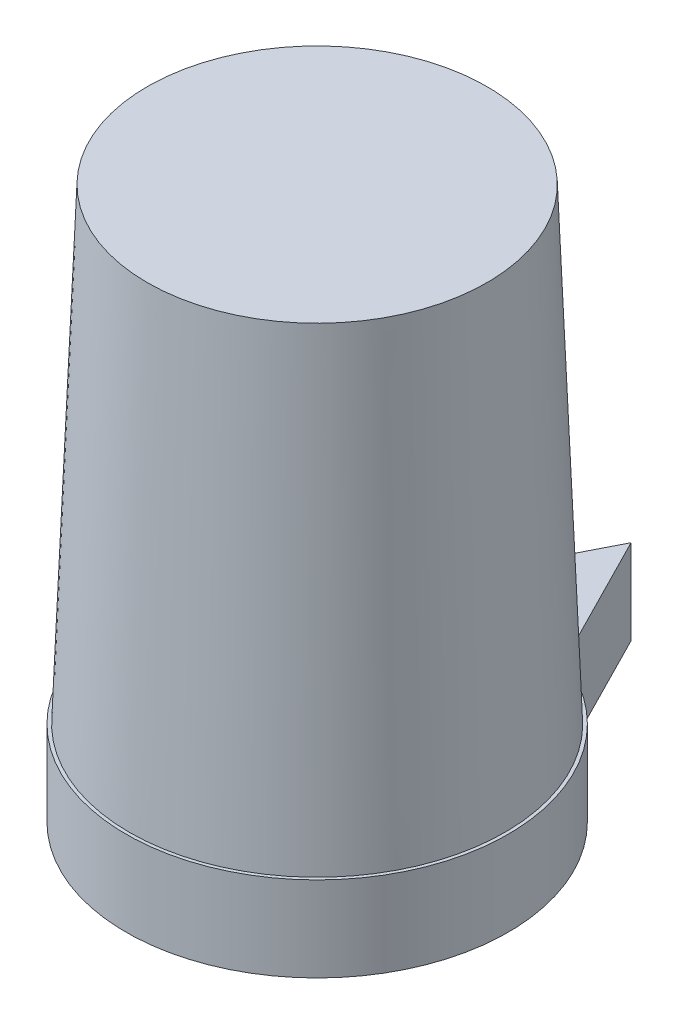
SolidWorks part; units mm, degrees
note: The reader was unsure of these and kept them because the rebuilt part matched: shared geometry of "Sketch1<35>", "Sketch1<36>".
ref_plane "Plan de face" through (0, 0, 0) normal (0, 0, 1) x (1, 0, 0)
ref_plane "Plan de dessus" through (0, 0, 0) normal (0, 1, 0) x (1, 0, 0)
ref_plane "Plan de droite" through (0, 0, 0) normal (1, 0, 0) x (0, 0, -1)
sketch "Sketch1" plane through (0, 0, 0) normal (0, 1, 0) x (1, 0, 0)
  line L0 (-3.4771, 0.4) -> (3.4771, 0.4)
  line L1 (-4.95, 0) -> (4.95, 0) construction
  line L2 (-3.4771, -0.4) -> (3.4771, -0.4)
  line L3 (-1.6263, 4.1959) -> (0, 7.3927)
  line L4 (0, -4.95) -> (0, 4.95) construction
  line L5 (1.6263, 4.1959) -> (0, 7.3927)
  circle A0 centre (0, 0) radius 3.5
  circle A1 centre (0, 0) radius 4.5
  point P12 (0, 0)
  point P16 (0, 7.945)
  point P17 (-1.6263, 4.1959)
  point P18 (0, 7.3927)
  dimension "D1" = 7
  dimension "D2" = 9
  dimension "D3" = 0.4
ref_plane "Plane1" through (0, 13, 0) normal (0, 1, 0) x (1, 0, 0)
sketch "Sketch2" plane through (0, 13, 0) normal (0, 1, 0) x (1, 0, 0)
  circle A0 centre (0, 0) radius 4
  dimension "D1" = 8
loft "Loft1" add profiles "Sketch2" section "Sketch2" section "Sketch1" connector at (-2.8461, 13, 2.8107) connector at (-3.4528, 0, 2.8858)
extrude "Boss-Extrude1" add sketch "Sketch1<35>" along normal blind 2 contours A1 L5 L3 | A1 A0
sketch "Sketch1<35>" plane through (0, 0, 0) normal (0, 1, 0) x (1, 0, 0) same geometry as "Sketch1"
extrude "Cut-Extrude1" cut sketch "Sketch1<36>" along normal blind 10 contours L2 A0 | L0 A0
sketch "Sketch1<36>" plane through (0, 0, 0) normal (0, 1, 0) x (1, 0, 0) same geometry as "Sketch1"
